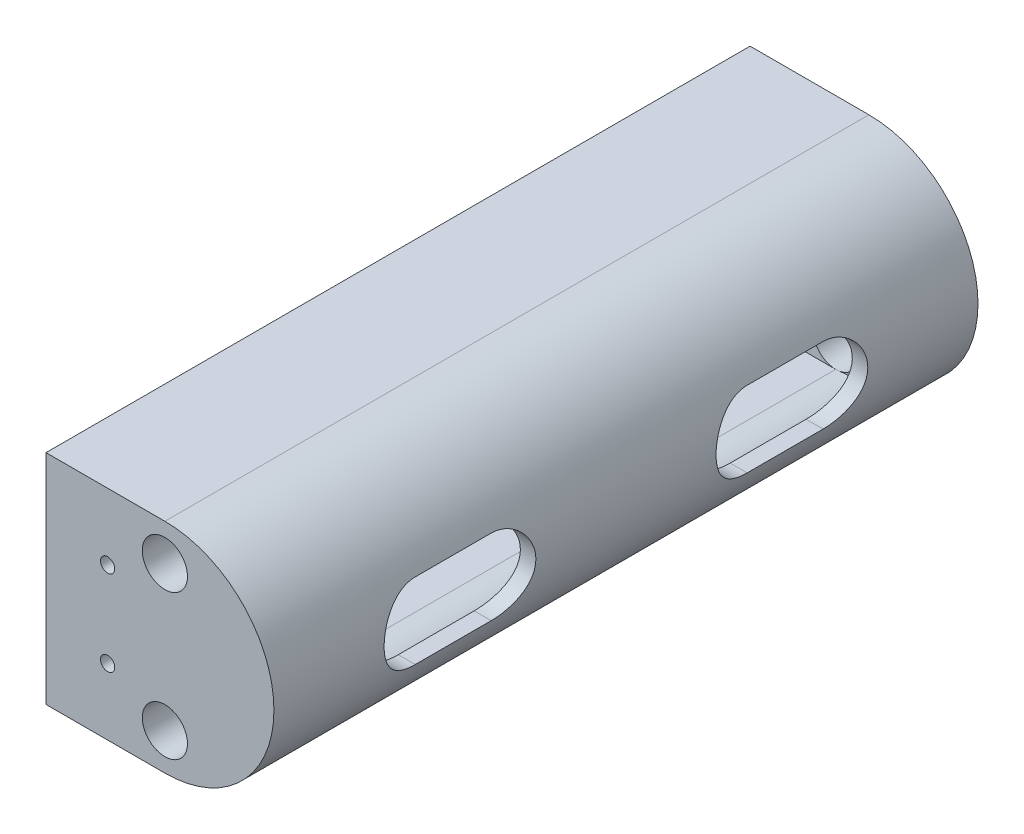
SolidWorks part; units mm, degrees
ref_plane "Alzado" through (0, 0, 0) normal (0, 0, 1) x (1, 0, 0)
ref_plane "Planta" through (0, 0, 0) normal (0, 1, 0) x (1, 0, 0)
ref_plane "Vista lateral" through (0, 0, 0) normal (1, 0, 0) x (0, 0, -1)
sketch "Croquis1" plane through (0, 0, 0) normal (0, 0, 1) x (1, 0, 0)
  line L0 (0, -20) -> (-11.3578, -20) construction
  line L1 (0, -20) -> (0, -23) construction
  line L2 (0, 23) -> (-25.07, 23)
  line L3 (0, 0) -> (-25.0698, -0.09) construction
  line L4 (-25.07, 23) -> (-25.07, -23)
  line L5 (-25.07, -23) -> (0, -23)
  line L6 (0, 23) -> (0, 29.8695) construction
  line L7 (0, 0) -> (0, -15.2375) construction
  line L8 (0, 29.8695) -> (-82.0465, 29.8695) construction
  line L9 (-58.3893, 29.8695) -> (0, 23) construction
  circle A0 centre (0, 0) radius 23
  circle A1 centre (0, -15.2375) radius 4.7625
  dimension "D1" = 46
  dimension "D4" = 9.525
  dimension "D2" = 3
  dimension "D3" = 173.29
  dimension "D5" = 23.09
  dimension "D6" = 22.91
extrude "Saliente-Extruir3" add sketch "Croquis1" along normal blind 7 contours A0 A1 | A0 L2 L4 | A0 L4 L5 region at (-23.5239, 0, 0) region at (0, 0.6826, 0)
sketch "Croquis3" plane through (0, 0, 7) normal (0, 0, 1) x (1, 0, 0)
  line L0 (0, 23) -> (-25.07, 23)
  line L1 (-25.07, -20) -> (0, -20)
  line L2 (-25.07, -23) -> (0, -23)
  line L3 (1.4962, 20.3997) -> (-25.07, 20)
  line L4 (-25.07, 23) -> (-25.07, 20)
  line L5 (-25.07, -20) -> (-25.07, -23)
  line L6 (-25.07, 23) -> (-25.07, -23) construction
  line L7 (0, 23) -> (-25.07, 23) construction
  arc A0 (0, -23) -> (0, 23) centre (0, 0) ccw
  arc A1 (0, -20) -> (1.4962, 20.3997) centre (-0.5199, 0.2468) ccw
  arc A2 (0, -23) -> (0, 23) centre (0, 0) ccw construction
  circle A3 centre (0, -15.2375) radius 4.7625 construction
  dimension "D1" = 3
  dimension "D4" = 3
  dimension "D2" = 3
  dimension "D3" = 3
extrude "Saliente-Extruir4" add sketch "Croquis3" along normal blind 134.48
sketch "Croquis4" plane through (0, 0, 141.48) normal (0, 0, 1) x (1, 0, 0)
  line L0 (0.1742, 25.1782) -> (-25.07, 23)
  line L1 (-25.07, 23) -> (-25.07, -23)
  line L2 (-25.07, -23) -> (0, -23)
  circle A0 centre (0, -15.2375) radius 4.7625
  circle A1 centre (0, -15.2375) radius 4.7625 construction
  circle A2 centre (0, 0) radius 25.07
  line M3 (-25.07, -20) -> (-25.07, -23)
  line M4 (-25.07, -23) -> (0, -23)
  arc M5 (0, -23) -> (0, 23) centre (0, 0) ccw
  line M6 (0, 23) -> (-25.07, 23)
  line M7 (-25.07, 23) -> (-25.07, 20)
  line M8 (-25.07, 20) -> (1.4962, 20.3997)
  arc M9 (1.4962, 20.3997) -> (0, -20) centre (-0.5199, 0.2468) cw
  line M10 (0, -20) -> (-25.07, -20)
extrude "Saliente-Extruir5" add sketch "Croquis4" along normal blind 7 contours A2 L1 M8 | A2 M6 M7 M8 | A2 A0 M8 M10 M9 | A2 M10 M3 M4 | A2 L1 M10 | A2 M5 M8 M9 M10 region at (-18.8471, 21.6361, 141.48) region at (-4.9876, 22.4026, 141.48) region at (-22.1745, 15.2806, 141.48) region at (-18.8372, -21.6034, 141.48) region at (-3.2806, 0.9157, 141.48) region at (-22.2228, -15.2201, 141.48)
sketch "Croquis5" plane through (-25.07, 0, 0) normal (-1, 0, 0) x (0, 0, 1)
  line L0 (74.24, 23) -> (74.24, -23) construction
  line L2 (148.48, -23) -> (0, -23) construction
  line L3 (0, 0) -> (74.24, 0) construction
  line L4 (31.24, 0) -> (47.24, 0) construction
  line L5 (31.24, 8) -> (47.24, 8)
  line L6 (31.24, -8) -> (47.24, -8)
  line L7 (117.24, 0) -> (101.24, 0) construction
  line L8 (117.24, 8) -> (101.24, 8)
  line L9 (117.24, -8) -> (101.24, -8)
  arc A0 (31.24, 8) -> (31.24, -8) centre (31.24, 0) ccw
  arc A1 (47.24, -8) -> (47.24, 8) centre (47.24, 0) ccw
  arc A2 (117.24, 8) -> (117.24, -8) centre (117.24, 0) cw
  arc A3 (101.24, -8) -> (101.24, 8) centre (101.24, 0) cw
  point P11 (39.24, 0)
  point P18 (109.24, 0)
  dimension "D1" = 8
  dimension "D2" = 16
  dimension "D3" = 35
extrude "Cortar-Extruir1" cut sketch "Croquis5" against normal through all
sketch "Croquis6" plane through (0, 0, 148.48) normal (0, 0, 1) x (1, 0, 0)
  line L0 (0, -15.2375) -> (0, 15.2925) construction
  circle A0 centre (0, 15.2925) radius 4.765
extrude "Cortar-Extruir2" cut sketch "Croquis6" against normal blind 190
sketch "Croquis7" plane through (0, 0, 148.48) normal (0, 0, 1) x (1, 0, 0)
  line L0 (-15.4029, 23) -> (-15.4029, 20) construction
  line L1 (0, 23) -> (-25.07, 23) construction
  line L2 (-15.4029, -23) -> (-15.4029, -20) construction
  line L3 (-25.07, -23) -> (0, -23) construction
  line L4 (-3.2298, -18.7375) -> (-3.2298, -11.7375) construction
  line L5 (-25.07, 23) -> (-25.07, -23) construction
  line L6 (-3.2298, -11.7375) -> (-25.07, -11.7375)
  line L7 (-3.2298, -11.7375) -> (-3.2298, -18.7375)
  line L8 (-3.2298, -18.7375) -> (-25.07, -18.7375)
  line L9 (-25.07, -11.7375) -> (-25.07, -18.7375)
  line L10 (0, 0) -> (-25.07, 0) construction
  line L11 (-3.2298, 18.7375) -> (-25.07, 18.7375)
  line L12 (-25.07, 11.7375) -> (-25.07, 18.7375)
  line L13 (-3.2298, 11.7375) -> (-25.07, 11.7375)
  line L14 (-3.2298, 11.7375) -> (-3.2298, 18.7375)
  circle A0 centre (0, -15.2375) radius 4.7625 construction
sketch "Croquis8" plane through (0, 0, 148.48) normal (0, 0, 1) x (1, 0, 0)
  line L0 (-25.07, 23) -> (-12.07, 23) construction
  line L1 (0, 23) -> (-25.07, 23) construction
  line L2 (-12.07, 23) -> (-12.07, 9) construction
  line L3 (-25.07, 0) -> (23, 0) construction
  line L4 (-25.07, 23) -> (-25.07, -23) construction
  circle A0 centre (-12.07, 9) radius 1.5
  arc A1 (0, -23) -> (0, 23) centre (0, 0) ccw construction
  circle A2 centre (-12.07, -9) radius 1.5
  dimension "D1" = 14
extrude "Cortar-Extruir3" cut sketch "Croquis8" against normal blind 154
